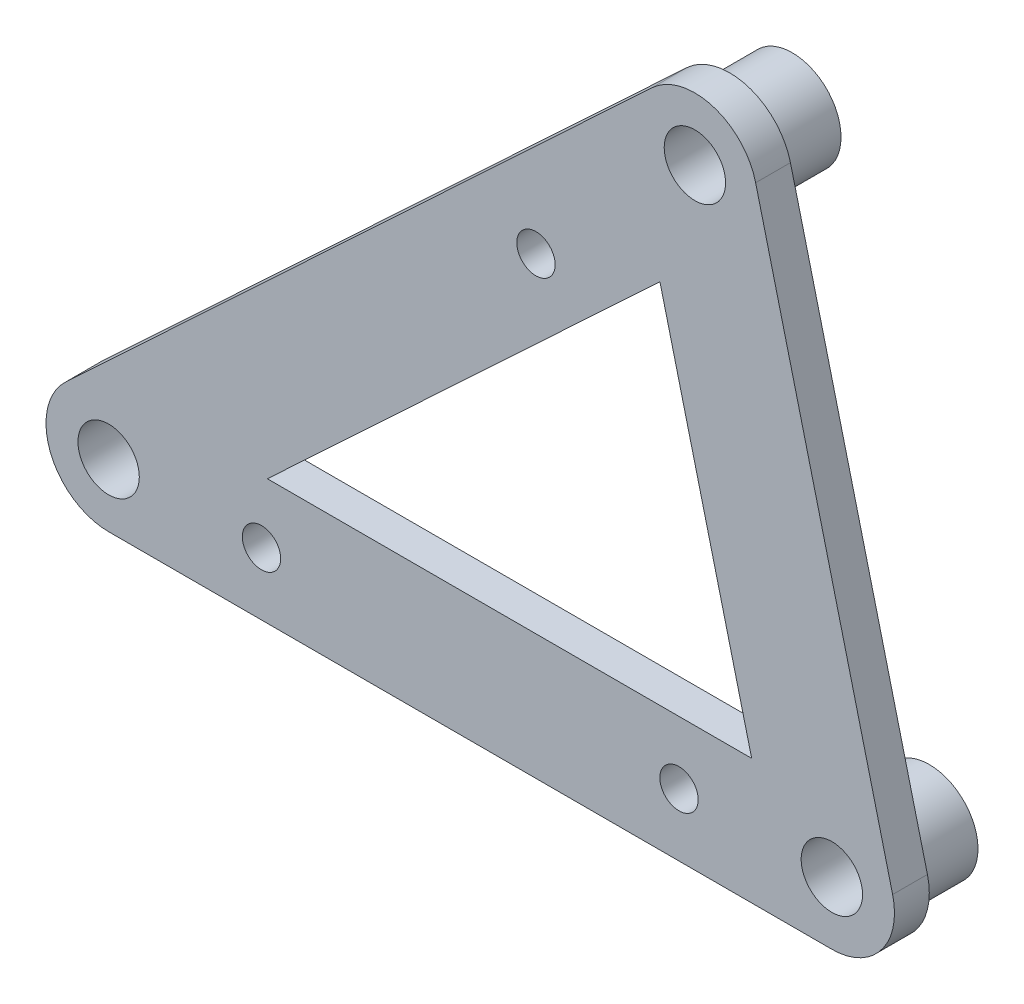
SolidWorks part; units mm, degrees
note: The reader was unsure of these and kept them because the rebuilt part matched: shared geometry of "Sketch2<3>".
ref_plane "Front Plane" through (0, 0, 0) normal (0, 0, 1) x (1, 0, 0)
ref_plane "Top Plane" through (0, 0, 0) normal (0, 1, 0) x (1, 0, 0)
ref_plane "Right Plane" through (0, 0, 0) normal (1, 0, 0) x (0, 0, -1)
sketch "Sketch1" plane through (0, 0, 0) normal (0, 0, 1) x (1, 0, 0)
  circle A0 centre (-25.5, -59.5) radius 2.8
  circle A1 centre (-91.5, -59.5) radius 2.8
  circle A3 centre (-38, -9.5) radius 2.8
  circle A4 centre (-91.5, -59.5) radius 4.445
  circle A5 centre (-25.5, -59.5) radius 4.445
  circle A6 centre (-38, -9.5) radius 4.445
  point P0 (-38, -9.5)
  point P1 (-4.5, -19.5)
  point P3 (-25.5, -59.5)
  point P5 (-91.5, -59.5)
  dimension "D1" = 5.6
  dimension "D3" = 5.6
  dimension "D4" = 5.6
  dimension "D5" = 8.89
extrude "Boss-Extrude1" add sketch "Sketch1" along normal blind 5.715
sketch "Sketch2" plane through (0, 0, 5.715) normal (0, 0, 1) x (1, 0, 0)
  line L0 (-25.5, -59.5) -> (-91.5, -59.5) construction
  line L1 (-25.5, -65.215) -> (-91.5, -65.215)
  line L2 (-25.5, -53.785) -> (-91.5, -53.785)
  line L3 (-25.5, -59.5) -> (-38, -9.5) construction
  line L4 (-31.0444, -60.8861) -> (-43.5444, -10.8861)
  line L5 (-19.9556, -58.1139) -> (-32.4556, -8.1139)
  line L6 (-38, -9.5) -> (-91.5, -59.5) construction
  line L7 (-34.0978, -13.6754) -> (-87.5978, -63.6754)
  line L8 (-41.9022, -5.3246) -> (-95.4022, -55.3246)
  arc A0 (-25.5, -65.215) -> (-25.5, -53.785) centre (-25.5, -59.5) ccw
  arc A1 (-91.5, -53.785) -> (-91.5, -65.215) centre (-91.5, -59.5) ccw
  arc A2 (-31.0444, -60.8861) -> (-19.9556, -58.1139) centre (-25.5, -59.5) ccw
  arc A3 (-32.4556, -8.1139) -> (-43.5444, -10.8861) centre (-38, -9.5) ccw
  arc A4 (-34.0978, -13.6754) -> (-41.9022, -5.3246) centre (-38, -9.5) ccw
  arc A5 (-95.4022, -55.3246) -> (-87.5978, -63.6754) centre (-91.5, -59.5) ccw
  circle A6 centre (-38, -9.5) radius 2.8
  circle A7 centre (-25.5, -59.5) radius 2.8
  circle A8 centre (-91.5, -59.5) radius 2.8
  point P0 (-25.5, -59.5)
  point P1 (-91.5, -59.5)
  point P6 (-58.5, -59.5)
  point P11 (-31.75, -34.5)
  point P20 (-64.75, -34.5)
  circle M1 centre (-25.5, -59.5) radius 4.445
  dimension "D1" = 11.43
  dimension "D2" = 11.43
  dimension "D3" = 11.43
extrude "Boss-Extrude5" add sketch "Sketch2" along normal blind 3.175 contours L7 A4 A3 L4 | A4 L7 L4 L2 A0 L5 | A3 L8 A1 L2 L7 L4 | A5 L1 A2 L4 L2 L7 | A1 A5 L7 L2 | L4 A2 A0 L2 M1
extrude "Boss-Extrude6" add sketch "Sketch2<3>" along normal blind 3.175
sketch "Sketch2<3>" plane through (0, 0, 5.715) normal (0, 0, 1) x (1, 0, 0) same geometry as "Sketch2"
sketch "Sketch3" plane through (0, 0, 8.89) normal (0, 0, 1) x (1, 0, 0)
  line L0 (-91.5, -59.5) -> (-25.5, -59.5)
  circle A0 centre (-77.55, -59.5) radius 1.75
  circle A1 centre (-39.45, -59.5) radius 1.75
  point P4 (-39.45, -59.5)
  point P5 (-77.55, -59.5)
  point P10 (-58.5, -59.5)
  dimension "D1" = 3.5
  dimension "D2" = 3.5
  dimension "D3" = 38.1
  dimension "D4" = 19.05
extrude "Cut-Extrude1" cut sketch "Sketch3" against normal blind 5.08 contours L0 A0 | L0 A0 | L0 A1 | L0 A1
sketch "Sketch4" plane through (0, 0, 5.715) normal (0, 0, -1) x (-1, 0, 0)
  circle A0 centre (52.5034, -23.7459) radius 1.75
extrude "Cut-Extrude2" cut sketch "Sketch4" against normal through all
